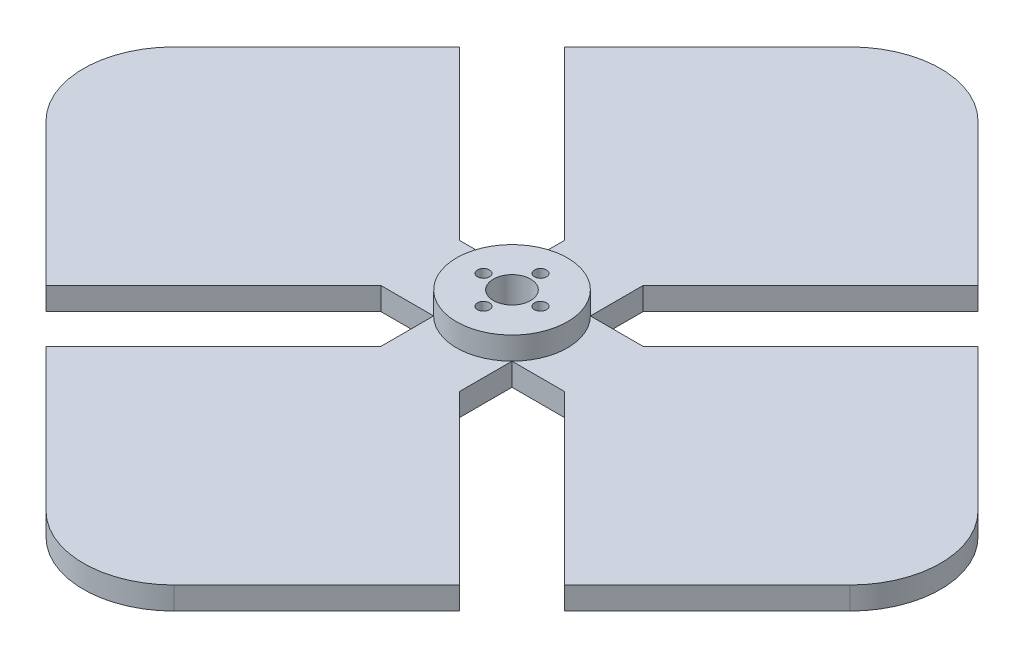
SolidWorks part; units mm, degrees
ref_plane "Front Plane" through (0, 0, 0) normal (0, 0, 1) x (1, 0, 0)
ref_plane "Top Plane" through (0, 0, 0) normal (0, 1, 0) x (1, 0, 0)
ref_plane "Right Plane" through (0, 0, 0) normal (1, 0, 0) x (0, 0, -1)
sketch "Sketch4" plane through (0, 0, 0) normal (0, 1, 0) x (1, 0, 0)
  line L8 (14.7955, 0) -> (72.808, -58.0125)
  line L9 (14.7955, 0) -> (72.808, 58.0125)
  line L10 (72.808, -58.0125) -> (130.8204, 0)
  line L11 (72.808, 58.0125) -> (130.8204, 0)
  line L13 (0, 11) -> (25.7955, 11)
  line L14 (0, 11) -> (0, -11)
  line L15 (0, -11) -> (25.7955, -11)
  line L16 (25.7955, 11) -> (25.7955, -11)
  dimension "D1" = 82.042
  dimension "D2" = 14.7955
  dimension "D3" = 22
extrude "Boss-Extrude5" add sketch "Sketch4" along normal blind 6.35 contours L9 L16 L8 L10 L11 | L16 L9 L8 | L14 L15 L8 L9 L13 region at (22.1288, 0, 0) region at (10.3962, 0, 0) region at (73.7357, 0, 0)
sketch "Sketch6" plane through (0, 0, 0) normal (0, 0, 1) x (1, 0, 0)
  line L0 (0, 0) -> (0, 27.64) construction
fillet "Fillet1" radius 25.4 1 edges at (130.8204, 3.175, 0)
pattern_circular "CirPattern7" count 4 over 360 about axis through (0, 0, 0) along (0, 1, 0) of "Boss-Extrude5", "Fillet1"
sketch "Sketch13" plane through (0, 6.35, 0) normal (0, 1, 0) x (1, 0, 0)
  circle A0 centre (0, 0) radius 15.5563
extrude "Boss-Extrude8" add sketch "Sketch13" along normal blind 6.35
sketch "Sketch1" plane through (0, 0, 0) normal (0, 1, 0) x (1, 0, 0)
  circle A0 centre (0, 0) radius 2.6905 construction
  circle A1 centre (0, 0) radius 5.227
  circle A2 centre (8, 0) radius 1.6865
  circle A6 centre (0, -8) radius 1.6865
  circle A7 centre (-8, 0) radius 1.6865
  circle A8 centre (0, 8) radius 1.6865
  point P15 (0, 0)
  dimension "D1" = 10.454
  dimension "D3" = 3.373
  dimension "D2" = 8
extrude "Cut-Extrude1" cut sketch "Sketch1" along normal through all
equation "\"tightTol\"= 0.005in"
equation "\"normTol\"= 0.01in"
equation "\"looseTol\"= 0.02in"
equation "\"D1@Sketch1\"=\"normTol\"+10.2mm"
equation "\"D2@Sketch1\"=8mm"
equation "\"D1@Sketch4\"=3.25-\"looseTol\""
equation "\"D2@Sketch4\"=9/16+\"looseTol\""
equation "\"D3@Sketch1\"=3.5mm-\"tightTol\""
